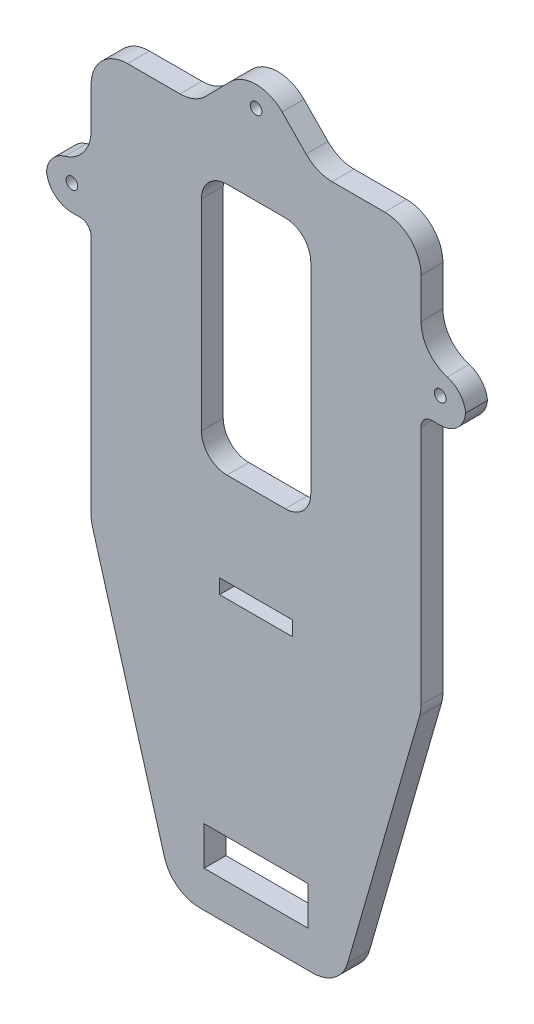
SolidWorks part; units mm, degrees
material "MDF"
ref_plane "Plano frontal" through (0, 0, 0) normal (0, 0, 1) x (1, 0, 0)
ref_plane "Plano superior" through (0, 0, 0) normal (0, 1, 0) x (1, 0, 0)
ref_plane "Plano direito" through (0, 0, 0) normal (1, 0, 0) x (0, 0, -1)
sketch "Esboço1" plane through (0, 0, 0) normal (0, 0, 1) x (1, 0, 0)
  line L1 (-45.25, -56.75) -> (45.25, -56.75) construction
  line L2 (-45.25, -56.75) -> (-45.25, 56.75) construction
  line L3 (-45.25, 56.75) -> (45.25, 56.75) construction
  line L4 (45.25, -56.75) -> (45.25, 13.75) construction
  line L5 (-45.25, -56.75) -> (45.25, 56.75) construction
  line L6 (-45.25, 56.75) -> (45.25, -56.75) construction
  line L18 (-45.25, -56.75) -> (21.552, -56.75) construction
  line L20 (-45.25, -56.75) -> (-23.0595, -133.85)
  line L21 (-23.0595, -133.85) -> (23.0595, -133.85)
  line L23 (14.25, -113.25) -> (-14.25, -113.25)
  line L24 (14.25, -113.25) -> (14.25, -123.85)
  line L25 (14.25, -123.85) -> (-14.25, -123.85)
  line L26 (-14.25, -113.25) -> (-14.25, -123.85)
  line L27 (14.25, -113.25) -> (-14.25, -123.85) construction
  line L28 (14.25, -123.85) -> (-14.25, -113.25) construction
  line L29 (-15.1, -125.35) -> (15.1, -125.35) construction
  line L30 (-15.1, -125.35) -> (-15.1, -111.75) construction
  line L31 (-15.1, -111.75) -> (15.1, -111.75) construction
  line L32 (15.1, -125.35) -> (15.1, -111.75) construction
  line L33 (-15.1, -125.35) -> (15.1, -111.75) construction
  line L34 (-15.1, -111.75) -> (15.1, -125.35) construction
  line L39 (-45.25, 25.75) -> (-45.25, 56.75)
  line L48 (15, -27.35) -> (-15, -27.35)
  line L50 (-45.25, 25.75) -> (-57.5, 25.75)
  line L52 (0, 0) -> (0, 36.35) construction
  line L54 (45.25, 25.75) -> (57.5, 25.75)
  line L55 (45.25, 25.75) -> (45.25, 56.75)
  line L56 (45.25, 25.75) -> (45.25, 56.75) construction
  line L57 (-45.25, 56.75) -> (-16.6633, 56.75)
  line L58 (-16.6633, 56.75) -> (0, 73.75)
  line L59 (0, 73.75) -> (16.6633, 56.75)
  line L60 (16.6633, 56.75) -> (45.25, 56.75)
  line L61 (-57.5, 25.75) -> (-57.5, 13.75)
  line L62 (-57.5, 13.75) -> (-45.25, 13.75)
  line L63 (57.5, 13.75) -> (45.25, 13.75)
  line L64 (57.5, 25.75) -> (57.5, 13.75)
  line L65 (23.0595, -133.85) -> (45.25, -56.75)
  line L66 (45.25, 13.75) -> (45.25, -56.75)
  line L67 (-45.25, -56.75) -> (-45.25, 13.75)
  line L68 (15, -27.35) -> (15, 41.75)
  line L69 (10, -52.75) -> (-10, -52.75)
  line L70 (10, -52.75) -> (10, -56.75)
  line L71 (10, -56.75) -> (-10, -56.75)
  line L72 (-10, -52.75) -> (-10, -56.75)
  line L73 (10, -52.75) -> (-10, -56.75) construction
  line L74 (10, -56.75) -> (-10, -52.75) construction
  line L75 (15, 41.75) -> (-15, 41.75)
  line L76 (-15, -27.35) -> (-15, 41.75)
  line L77 (15, -27.35) -> (-15, 41.75) construction
  line L78 (15, 41.75) -> (-15, -27.35) construction
  circle A0 centre (0, 63.75) radius 1.6
  circle A1 centre (-50.5, -80.53) radius 1.6
  circle A2 centre (-50.5, 20.75) radius 1.6
  circle A3 centre (50.5, 20.75) radius 1.6
  point P0 (0, 0)
  point P6 (0, -54.75)
  point P16 (0, -133.85)
  point P27 (0, -118.55)
  point P32 (0, -118.55)
  point P39 (0, 0)
  point P42 (0, 7.2)
  dimension "D3" = 3.2
  dimension "D10" = 10
  dimension "D4" = 7
  dimension "D5" = 10
  dimension "D9" = 43
  dimension "D19" = 101
  dimension "D1" = 90.5
  dimension "D2" = 113.5
  dimension "D6" = 5
  dimension "D7" = 55
  dimension "D8" = 10
  dimension "D11" = 28.5
  dimension "D12" = 10.6
  dimension "D13" = 13.6
  dimension "D14" = 30.2
  dimension "D15" = 7
  dimension "D16" = 144.28
  dimension "D17" = 25.4
  dimension "D18" = 7
  dimension "D20" = 15
  dimension "D21" = 20
  dimension "D22" = 7
  dimension "D23" = 4
  dimension "D24" = 30
extrude "Ressalto-extrusão1" add sketch "Esboço1" along normal blind 6 contours L23 L24 L25 | L26 L23 L25 A2 A1 A0 region at (0, -31.6811, 0)
fillet "Filete3" radius 3 2 edges at (45.25, 13.75, 3) (-45.25, 13.75, 3)
fillet "Filete4" radius 10 11 edges at (-16.6633, 56.75, 3) (16.6633, 56.75, 3) (-45.25, 25.75, 3) (45.25, 25.75, 3) (0, 73.75, 3) (45.25, 56.75, 3) (-45.25, 56.75, 3) (-45.25, -56.75, 3) (45.25, -56.75, 3) (23.0595, -133.85, 3) (-23.0595, -133.85, 3)
fillet "Filete5" radius 7 8 edges at (57.5, 13.75, 3) (57.5, 25.75, 3) (-57.5, 13.75, 3) (-57.5, 25.75, 3) (-15, -27.35, 3) (15, -27.35, 3) (15, 41.75, 3) (-15, 41.75, 3)
equation "\"mm\"=5"
